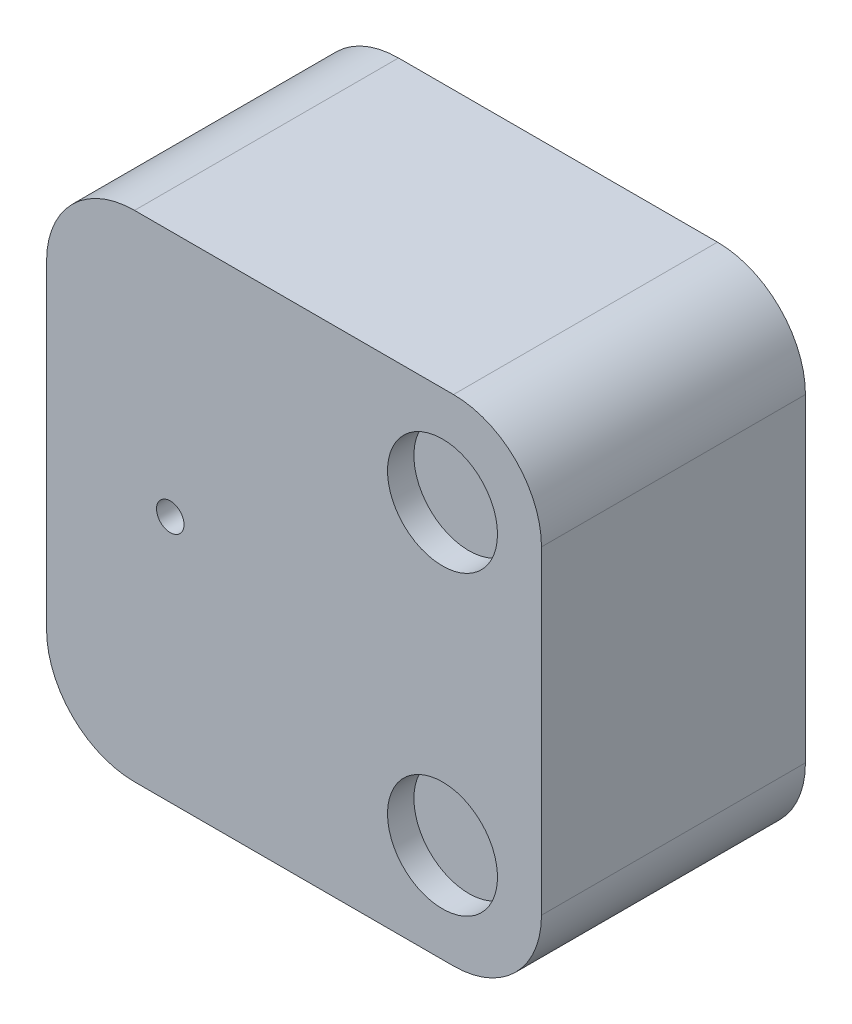
SolidWorks part; units mm, degrees
ref_plane "Plan de face" through (0, 0, 0) normal (0, 0, 1) x (1, 0, 0)
ref_plane "Plan de dessus" through (0, 0, 0) normal (0, 1, 0) x (1, 0, 0)
ref_plane "Plan de droite" through (0, 0, 0) normal (1, 0, 0) x (0, 0, -1)
other "Centre de masse"
sketch "Esquisse1" plane through (0, 0, 0) normal (0, 0, 1) x (1, 0, 0)
  line L1 (-90, -90) -> (90, -90)
  line L2 (-90, -90) -> (-90, 90)
  line L3 (-90, 90) -> (90, 90)
  line L4 (90, -90) -> (90, 90)
  line L5 (-90, -90) -> (90, 90) construction
  line L6 (-90, 90) -> (90, -90) construction
  point P0 (0, 0)
  dimension "D1" = 180
  dimension "D2" = 180
extrude "Boss.-Extru.1" add sketch "Esquisse1" along normal blind 96
fillet "Congé1" radius 32 4 edges at (-90, 90, 48) (-90, -90, 48) (90, -90, 48) (90, 90, 48)
sketch "Esquisse2" plane through (0, 0, 96) normal (0, 0, 1) x (1, 0, 0)
  line L0 (58, 90) -> (-58, 90) construction
  line L1 (2.5426, 0) -> (67.0148, 0) construction
  line L2 (90, -58) -> (90, 58) construction
  line L3 (-90, 35.3964) -> (-90, -5.661) construction
  line L4 (-90, 58) -> (-90, -58) construction
  circle A0 centre (54, 54) radius 20
  circle A1 centre (54, -54) radius 20
  circle A2 centre (-45, 0) radius 5
  dimension "D1" = 40
  dimension "D4" = 10
  dimension "D2" = 36
  dimension "D3" = 36
  dimension "D5" = 45
  dimension "D6" = 90
extrude "Enlèv. mat.-Extru.1" cut sketch "Esquisse2" against normal blind 9.6
ref_axis "Axe1" through (0, 0, 0) along (0, 0, 1)
ref_point "Point1"
equation "\"L\"= 0.18m"
equation "\"D2@Esquisse1\"=\"L\""
equation "\"D1@Esquisse1\"=\"L\""
equation "\"e\"= 0.096m"
equation "\"D1@Boss.-Extru.1\"=\"e\""
equation "\"D1@Congé1\"=\"e\"/3m"
equation "\"D2@Esquisse2\"=\"L\"/5m"
equation "\"D3@Esquisse2\"=\"L\"/5"
equation "\"D\"= 0.04m"
equation "\"D1@Esquisse2\"=\"D\""
equation "\"D1@Enlèv. mat.-Extru.1\"=\"e\"/10"
equation "\"D5@Esquisse2\"=\"L\"/4"
